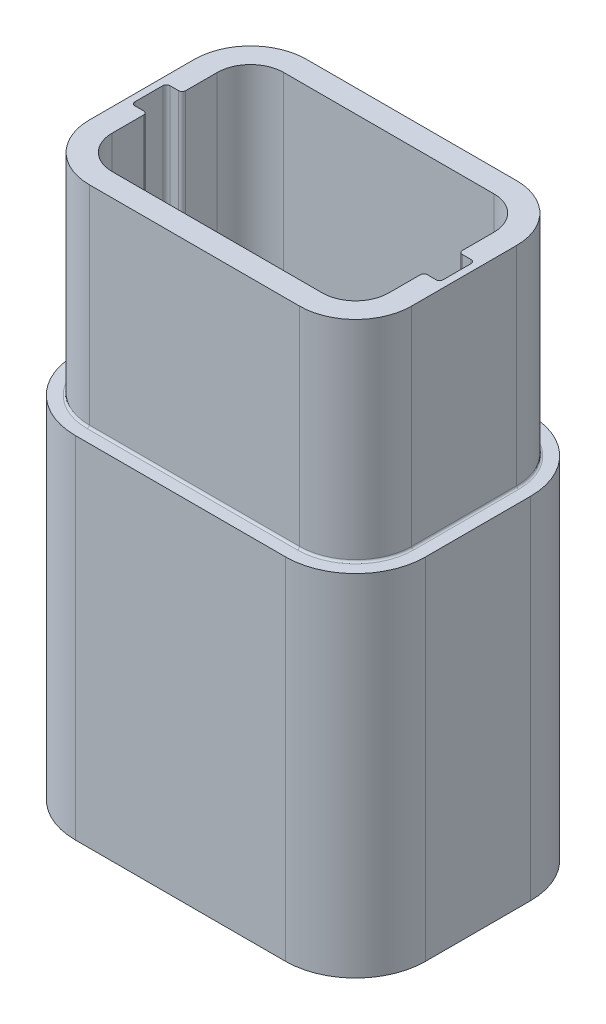
SolidWorks part; units mm, degrees
ref_plane "Alzado" through (0, 0, 0) normal (0, 0, 1) x (1, 0, 0)
ref_plane "Planta" through (0, 0, 0) normal (0, 1, 0) x (1, 0, 0)
ref_plane "Vista lateral" through (0, 0, 0) normal (1, 0, 0) x (0, 0, -1)
sketch "Croquis1" plane through (0, 0, 0) normal (0, 1, 0) x (1, 0, 0)
  line L1 (-15, 17.5) -> (15, 17.5)
  line L2 (-25, 7.5) -> (-25, -7.5)
  line L3 (-15, -17.5) -> (15, -17.5)
  line L4 (25, 7.5) -> (25, -7.5)
  line L5 (-25, 17.5) -> (25, -17.5) construction
  line L6 (-25, -17.5) -> (25, 17.5) construction
  arc A0 (15, 17.5) -> (25, 7.5) centre (15, 7.5) cw
  arc A1 (15, -17.5) -> (25, -7.5) centre (15, -7.5) ccw
  arc A2 (-25, -7.5) -> (-15, -17.5) centre (-15, -7.5) ccw
  arc A3 (-15, 17.5) -> (-25, 7.5) centre (-15, 7.5) ccw
  point P0 (0, 0)
  dimension "D3" = 10
  dimension "D1" = 50
  dimension "D2" = 35
extrude "Saliente-Extruir1" add sketch "Croquis1" along normal blind 50
sketch "Croquis2" plane through (0, 50, 0) normal (0, 1, 0) x (1, 0, 0)
  line L8 (15, 15.5) -> (-15, 15.5)
  line L9 (-23, 7.5) -> (-23, -7.5)
  line L10 (-15, -15.5) -> (15, -15.5)
  line L11 (23, -7.5) -> (23, 7.5)
  line L12 (15, 15.5) -> (-15, 15.5)
  line L13 (-23, 7.5) -> (-23, -7.5)
  line L14 (-15, -15.5) -> (15, -15.5)
  line L15 (23, -7.5) -> (23, 7.5)
  arc A8 (23, 7.5) -> (15, 15.5) centre (15, 7.5) ccw
  arc A9 (-15, 15.5) -> (-23, 7.5) centre (-15, 7.5) ccw
  arc A10 (-23, -7.5) -> (-15, -15.5) centre (-15, -7.5) ccw
  arc A11 (15, -15.5) -> (23, -7.5) centre (15, -7.5) ccw
  arc A12 (23, 7.5) -> (15, 15.5) centre (15, 7.5) ccw
  arc A13 (-15, 15.5) -> (-23, 7.5) centre (-15, 7.5) ccw
  arc A14 (-23, -7.5) -> (-15, -15.5) centre (-15, -7.5) ccw
  arc A15 (15, -15.5) -> (23, -7.5) centre (15, -7.5) ccw
  dimension "D1" = 2
extrude "Saliente-Extruir2" add sketch "Croquis2" along normal blind 30
shell "Vaciado2" thickness 5.25 removed face at (0, 80, 0)
fillet "Redondeo1" radius 0.3 8 edges at (-20.6569, 50, 13.1569) (-23, 50, 0) (-20.6569, 50, -13.1569) (0, 50, -15.5) (20.6569, 50, -13.1569) (23, 50, 0) (20.6569, 50, 13.1569) (0, 50, 15.5)
sketch "Croquis3" plane through (0, 5.25, 0) normal (0, 1, 0) x (1, 0, 0)
  circle A0 centre (0, 0) radius 7.5
  dimension "D1" = 15
extrude "Cortar-Extruir1" cut sketch "Croquis3" against normal up to next
sketch "Croquis6" plane through (0, 44.75, 0) normal (0, -1, 0) x (1, 0, 0)
  line L0 (15, 10.25) -> (-15, 10.25)
  line L1 (-17.75, 7.5) -> (-17.75, -7.5)
  line L2 (-15, -10.25) -> (15, -10.25)
  line L3 (17.75, -7.5) -> (17.75, 7.5)
  line L4 (19.75, -7.5) -> (19.75, 7.5)
  line L5 (15, 12.25) -> (-15, 12.25)
  line L6 (-19.75, 7.5) -> (-19.75, -7.5)
  line L7 (-15, -12.25) -> (15, -12.25)
  line L8 (19.75, -7.5) -> (19.75, 7.5)
  line L9 (15, 12.25) -> (-15, 12.25)
  line L10 (-19.75, 7.5) -> (-19.75, -7.5)
  line L11 (-15, -12.25) -> (15, -12.25)
  arc A0 (-15, 10.25) -> (-17.75, 7.5) centre (-15, 7.5) ccw
  arc A1 (-17.75, -7.5) -> (-15, -10.25) centre (-15, -7.5) ccw
  arc A2 (15, -10.25) -> (17.75, -7.5) centre (15, -7.5) ccw
  arc A3 (17.75, 7.5) -> (15, 10.25) centre (15, 7.5) ccw
  arc A4 (15, -12.25) -> (19.75, -7.5) centre (15, -7.5) ccw
  arc A5 (19.75, 7.5) -> (15, 12.25) centre (15, 7.5) ccw
  arc A6 (-15, 12.25) -> (-19.75, 7.5) centre (-15, 7.5) ccw
  arc A7 (-19.75, -7.5) -> (-15, -12.25) centre (-15, -7.5) ccw
  arc A8 (15, -12.25) -> (19.75, -7.5) centre (15, -7.5) ccw
  arc A9 (19.75, 7.5) -> (15, 12.25) centre (15, 7.5) ccw
  arc A10 (-15, 12.25) -> (-19.75, 7.5) centre (-15, 7.5) ccw
  arc A11 (-19.75, -7.5) -> (-15, -12.25) centre (-15, -7.5) ccw
  dimension "D1" = 0
  dimension "D2" = 2
extrude "Cortar-Extruir3" cut sketch "Croquis6" against normal up to surface (35.25 mm away) up to face at (0, 80, 0)
sketch "Croquis7" plane through (0, 5.25, 0) normal (0, 1, 0) x (1, 0, 0)
  line L0 (-23, 7.5) -> (-23, -7.5) construction
  line L1 (-22, 2.5) -> (-19, 2.5)
  line L2 (-22, 2.5) -> (-22, -2.5)
  line L3 (-22, -2.5) -> (-19, -2.5)
  line L4 (-19, 2.5) -> (-19, -2.5)
  line L5 (0, -12.25) -> (0, 12.25) construction
  line L6 (15, 12.25) -> (-15, 12.25) construction
  line L7 (22, -2.5) -> (19, -2.5)
  line L8 (19, 2.5) -> (19, -2.5)
  line L9 (22, 2.5) -> (19, 2.5)
  line L10 (22, 2.5) -> (22, -2.5)
  point P6 (-19, 0)
  point P13 (0, 0)
  dimension "D1" = 1
  dimension "D2" = 3
  dimension "D3" = 5
extrude "Cortar-Extruir4" cut sketch "Croquis7" along normal up to surface (74.75 mm away) up to face at (0, 80, 0)
fillet "Redondeo7" radius 0.5 8 edges at (19.75, 42.625, 2.5) (19.75, 42.625, -2.5) (-19.75, 42.625, 2.5) (-19.75, 42.625, -2.5) (-22, 42.625, 2.5) (-22, 42.625, -2.5) (22, 42.625, 2.5) (22, 42.625, -2.5)
sketch "Croquis8" plane through (0, 5.25, 0) normal (0, 1, 0) x (1, 0, 0)
  line L0 (0, -7.5) -> (0, 7.5) construction
  line L1 (-7.5, 0) -> (7.5, 0) construction
  line L3 (-1.5, 10.0711) -> (1.5, 10.0711)
  line L4 (-2.5, 9.0711) -> (-2.5, 7.0711)
  line L5 (-2.5, 7.0711) -> (2.5, 7.0711)
  line L6 (2.5, 9.0711) -> (2.5, 7.0711)
  line L8 (9.0711, 2.5) -> (7.0711, 2.5)
  line L9 (10.0711, 1.5) -> (10.0711, -1.5)
  line L10 (9.0711, -2.5) -> (7.0711, -2.5)
  line L11 (7.0711, 2.5) -> (7.0711, -2.5)
  line L12 (2.5, -9.0711) -> (2.5, -7.0711)
  line L13 (1.5, -10.0711) -> (-1.5, -10.0711)
  line L14 (-2.5, -9.0711) -> (-2.5, -7.0711)
  line L15 (2.5, -7.0711) -> (-2.5, -7.0711)
  line L16 (-9.0711, -2.5) -> (-7.0711, -2.5)
  line L17 (-10.0711, -1.5) -> (-10.0711, 1.5)
  line L18 (-9.0711, 2.5) -> (-7.0711, 2.5)
  line L19 (-7.0711, -2.5) -> (-7.0711, 2.5)
  arc A8 (2.5, 9.0711) -> (1.5, 10.0711) centre (1.5, 9.0711) ccw
  circle A9 centre (0, 0) radius 7.5 construction
  arc A10 (-2.5, 9.0711) -> (-1.5, 10.0711) centre (-1.5, 9.0711) cw
  arc A11 (9.0711, 2.5) -> (10.0711, 1.5) centre (9.0711, 1.5) cw
  arc A12 (9.0711, -2.5) -> (10.0711, -1.5) centre (9.0711, -1.5) ccw
  arc A13 (2.5, -9.0711) -> (1.5, -10.0711) centre (1.5, -9.0711) cw
  arc A14 (-2.5, -9.0711) -> (-1.5, -10.0711) centre (-1.5, -9.0711) ccw
  arc A15 (-9.0711, -2.5) -> (-10.0711, -1.5) centre (-9.0711, -1.5) cw
  arc A16 (-9.0711, 2.5) -> (-10.0711, 1.5) centre (-9.0711, 1.5) ccw
  point P5 (0, 0)
  point P8 (0, 0)
  point P14 (0, 10.0711)
  point P17 (2.5, 10.0711)
  point P45 (0, 0)
  dimension "D2" = 3
  dimension "D3" = 1
  dimension "D1" = 5
  dimension "D4" = 4
extrude "Cortar-Extruir5" cut sketch "Croquis8" against normal up to next
